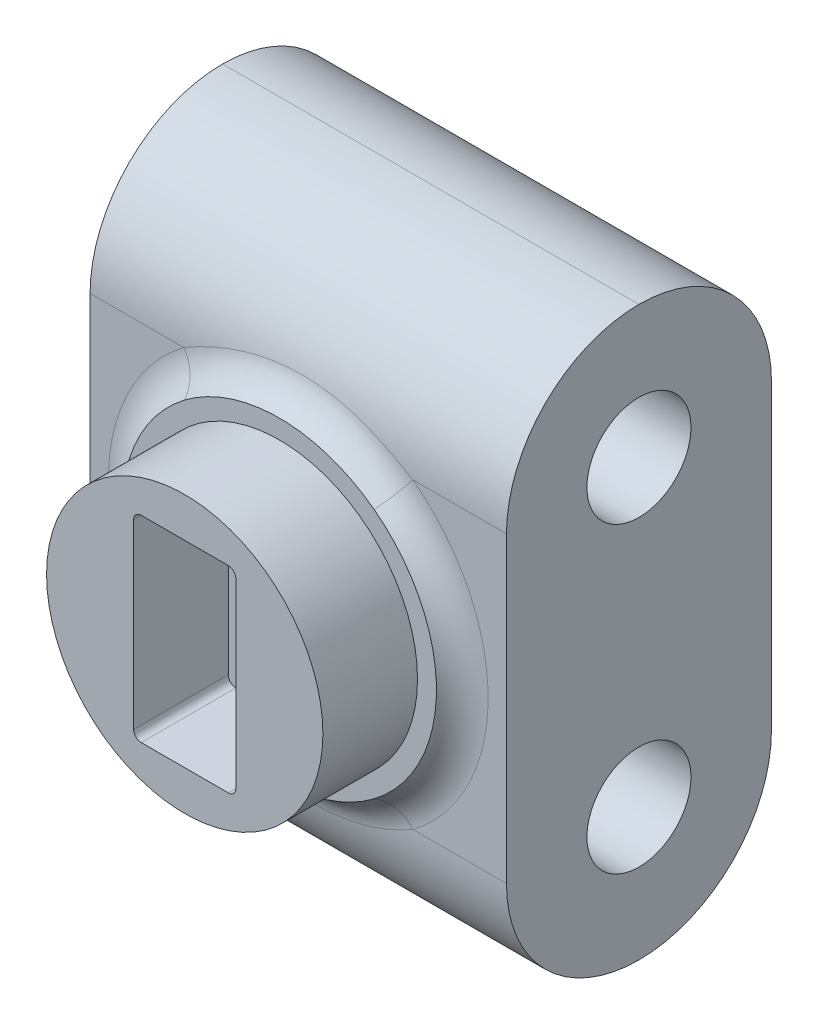
SolidWorks part; units mm, degrees
ref_plane "Спереди" through (0, 0, 0) normal (0, 0, 1) x (1, 0, 0)
ref_plane "Сверху" through (0, 0, 0) normal (0, 1, 0) x (1, 0, 0)
ref_plane "Справа" through (0, 0, 0) normal (1, 0, 0) x (0, 0, -1)
sketch "Эскиз1" plane through (0, 0, 0) normal (0, 0, 1) x (1, 0, 0)
  circle A0 centre (0, 0) radius 7.5 construction
  circle A1 centre (0, 0) radius 7.3
  dimension "D1" = 15
  dimension "measurement_tolerance" = 0.2
extrude "Бобышка-Вытянуть1" add sketch "Эскиз1" along normal blind 5
sketch "Эскиз2" plane through (0, 0, 0) normal (0, 0, -1) x (-1, 0, 0)
  circle A2 centre (0, 0) radius 8.3
  circle A3 centre (0, 0) radius 8.3
  dimension "D1" = 1
extrude "Бобышка-Вытянуть2" add sketch "Эскиз2" along normal blind 1
sketch "Эскиз3" plane through (0, 0, -1) normal (0, 0, -1) x (-1, 0, 0)
  line L0 (0, 15) -> (0, -15) construction
  line L1 (11, 15) -> (-11, 15)
  line L2 (-11, 15) -> (-11, -15)
  line L3 (-11, -15) -> (11, -15)
  line L4 (11, 15) -> (11, -15)
  line L5 (0, 0) -> (11, 0) construction
  dimension "D1" = 22
  dimension "D2" = 15
  dimension "D3" = 15
extrude "Бобышка-Вытянуть3" add sketch "Эскиз3" along normal blind 14
fillet "Скругление1" radius 7 4 edges at (0, 15, -1) (0, 15, -15) (0, -15, -15) (0, -15, -1)
hole_wizard "Отверстие с зазором M51" positions "Эскиз5" profile "Эскиз4" hole size "M5" standard "Ansi Metric" end condition through all
sketch "Эскиз5" plane through (11, 0, 0) normal (1, 0, 0) x (0, 0, -1)
  line L0 (8, 15) -> (8, -15) construction
  line L4 (1, 0) -> (15, 0) construction
  line L5 (1, 8) -> (1, -8) construction
  line L6 (15, 8) -> (15, -8) construction
  arc A0 (8, 15) -> (1, 8) centre (8, 8) ccw construction
  point P0 (8, 8)
  point P19 (8, -8)
sketch "Эскиз4" plane through (11, 8, -8) normal (0, 1, 0) x (0, 0, -1)
  line L0 (0, 0) -> (0, 22)
  line L1 (0, 22) -> (2.75, 22)
  line L2 (2.75, 22) -> (2.75, 0)
  line L5 (2.75, 0) -> (0, 0)
  line L11 (0, -6.35) -> (0, 107.95) construction
  dimension "Диаметр сквозного отверстия" = 5.5
  dimension "Глубина сквозного отверстия" = 22
sketch "Эскиз6" plane through (0, 0, 5) normal (0, 0, 1) x (1, 0, 0)
  line L1 (-2.7, -5.2) -> (2.7, -5.2)
  line L2 (-2.7, -5.2) -> (-2.7, 5.2)
  line L3 (-2.7, 5.2) -> (2.7, 5.2)
  line L4 (2.7, -5.2) -> (2.7, 5.2)
  line L5 (-2.7, -5.2) -> (2.7, 5.2) construction
  line L6 (-2.7, 5.2) -> (2.7, -5.2) construction
  point P0 (0, 0)
  dimension "D1" = 10.4
  dimension "D2" = 5.4
extrude "Вырез-Вытянуть1" cut sketch "Эскиз6" against normal blind 5
fillet "Скругление2" radius 0.4 4 edges at (-2.7, 5.2, 2.5) (-2.7, -5.2, 2.5) (2.7, -5.2, 2.5) (2.7, 5.2, 2.5)
fillet "Скругление4" radius 2 4 edges at (0.561, -8.281, -1.0056) (8.3, 0, -1) (-0.561, 8.281, -1.0056) (-8.3, 0, -1)
